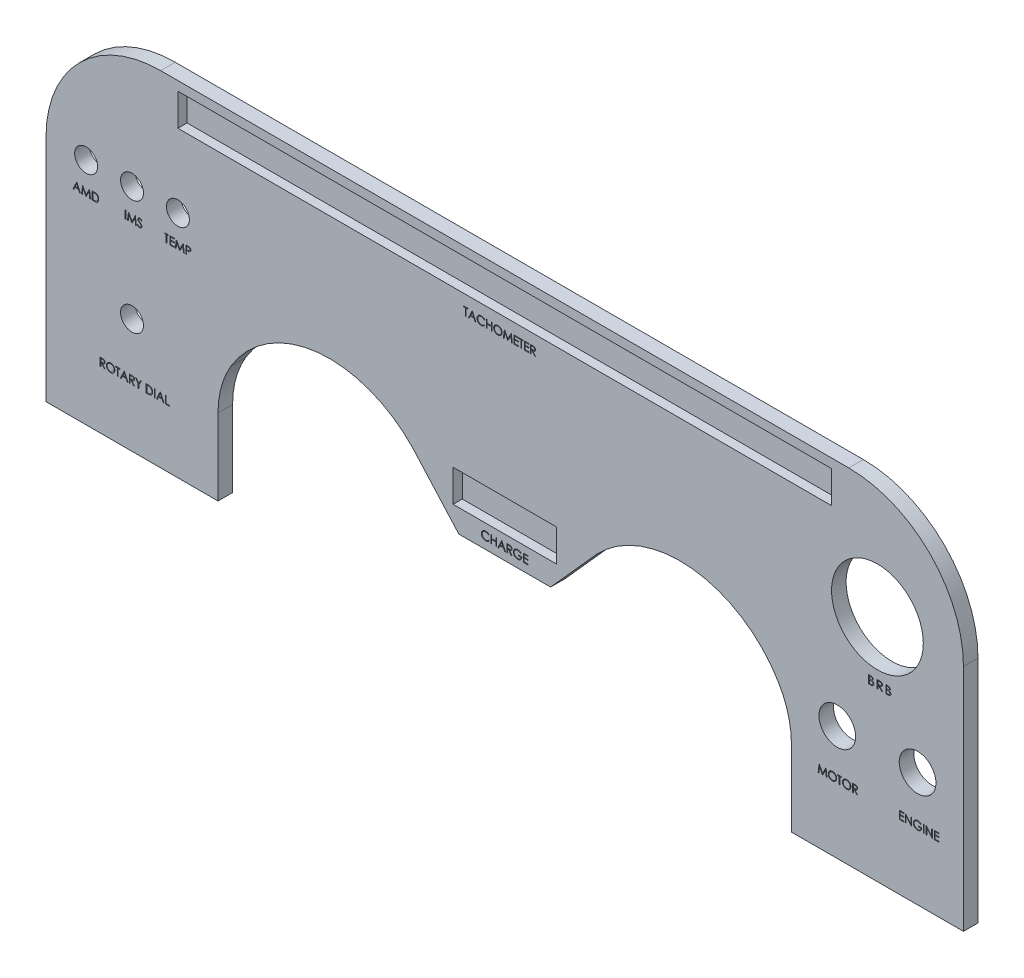
SolidWorks part; units mm, degrees
ref_plane "Front Plane" through (0, 0, 0) normal (0, 0, 1) x (1, 0, 0)
ref_plane "Top Plane" through (0, 0, 0) normal (0, 1, 0) x (1, 0, 0)
ref_plane "Right Plane" through (0, 0, 0) normal (1, 0, 0) x (0, 0, -1)
sketch "Sketch1" plane through (0, 0, 0) normal (0, 0, 1) x (1, 0, 0)
  line L0 (0, 0) -> (75, 0)
  line L1 (400, 0) -> (400, 150)
  line L2 (400, 150) -> (0, 150)
  line L3 (0, 150) -> (0, 0)
  line L4 (200, 150) -> (200, 40) construction
  line L5 (75, 0) -> (75, 40)
  line L6 (75, 40) -> (325, 40)
  line L7 (325, 0) -> (325, 40)
  line L8 (325, 0) -> (400, 0)
  line L9 (180, 40) -> (160, 62.3607)
  line L10 (220, 40) -> (240, 62.3607)
  arc A0 (75, 40) -> (160, 62.3607) centre (123.5673, 28.1166) cw
  arc A1 (325, 40) -> (240, 62.3607) centre (276.4327, 28.1166) ccw
  point P11 (200, 40)
  point P15 (110.8468, 76.4714)
  dimension "D7" = 30
  dimension "D8" = 50
  dimension "D1" = 400
  dimension "D2" = 150
  dimension "D3" = 40
  dimension "D4" = 125
  dimension "D5" = 20
  dimension "D6" = 40
extrude "Boss-Extrude1" add sketch "Sketch1" along normal blind 6.35 contours L4 L2 L3 L0 L5 A0 L9 L6 | L2 L4 L6 L10 A1 L7 L8 L1 region at (88.4336, 89.8407, 0) region at (311.5664, 89.8407, 0)
fillet "Fillet1" radius 50 2 edges at (400, 150, 3.175) (0, 150, 3.175)
sketch "Sketch2" plane through (0, 0, 6.35) normal (0, 0, 1) x (1, 0, 0)
  line L0 (0, 100) -> (0, 0) construction
  line L1 (0, 0) -> (75, 0) construction
  line L2 (325, 0) -> (400, 0) construction
  line L3 (400, 0) -> (400, 100) construction
  line L4 (350, 150) -> (50, 150) construction
  line L9 (180, 40) -> (220, 40) construction
  line L14 (200, 40) -> (200, 150) construction
  circle A2 centre (362.5, 100) radius 20
  circle A6 centre (37.5, 50) radius 5
  circle A7 centre (37.5, 100) radius 5
  circle A8 centre (17.5, 100) radius 5
  circle A9 centre (57.5, 100) radius 5
  circle A10 centre (345, 50) radius 8
  circle A11 centre (380, 50) radius 8
  dimension "D1" = 40
  dimension "D2" = 10
  dimension "D3" = 10
  dimension "D4" = 10
  dimension "D10" = 37.5
  dimension "D12" = 10
  dimension "D16" = 16
  dimension "D17" = 16
  dimension "D5" = 100
  dimension "D6" = 100
  dimension "D7" = 100
  dimension "D8" = 37.5
  dimension "D9" = 50
  dimension "D11" = 20
  dimension "D13" = 20
  dimension "D14" = 100
  dimension "D15" = 37.5
  dimension "D18" = 20
  dimension "D19" = 35
  dimension "D20" = 50
  dimension "D21" = 50
extrude "Cut-Extrude1" cut sketch "Sketch2" against normal through all contours A6
extrude "Cut-Extrude3" cut sketch "Sketch2<6>" against normal through all
sketch "Sketch2<6>" plane through (0, 0, 6.35) normal (0, 0, 1) x (1, 0, 0) same geometry as "Sketch2"
fillet "Fillet2" radius 40 1 edges at (75, 40, 3.175)
fillet "Fillet3" radius 40 1 edges at (325, 40, 3.175)
sketch "Sketch3" plane through (0, 0, 6.35) normal (0, 0, 1) x (1, 0, 0)
  text T0 "BRB" font "Century Gothic" height 3.5
extrude "Cut-Extrude4" cut sketch "Sketch3" against normal blind 2
sketch "Sketch4" plane through (0, 0, 6.35) normal (0, 0, 1) x (1, 0, 0)
  text T0 "MOTOR             ENGINE" font "Century Gothic" height 3.5
sketch "Sketch5" plane through (0, 0, 6.35) normal (0, 0, 1) x (1, 0, 0)
  text T0 "ROTARY DIAL"
sketch "Sketch6" plane through (0, 0, 6.35) normal (0, 0, 1) x (1, 0, 0)
  text T0 "AMD        IMS       TEMP"
extrude "Cut-Extrude5" cut sketch "Sketch6" against normal blind 2
extrude "Cut-Extrude6" cut sketch "Sketch5" against normal blind 2
extrude "Cut-Extrude7" cut sketch "Sketch4" against normal blind 2
sketch "Sketch7" plane through (0, 0, 6.35) normal (0, 0, 1) x (1, 0, 0)
  line L0 (350, 150) -> (50, 150) construction
  line L1 (57.5, 146) -> (342.5, 146)
  line L2 (57.5, 146) -> (57.5, 132)
  line L3 (57.5, 132) -> (342.5, 132)
  line L4 (342.5, 146) -> (342.5, 132)
  line L5 (200, 40) -> (200, 150) construction
  line L6 (180, 40) -> (220, 40) construction
  line L8 (177.5, 64) -> (222.5, 64)
  line L9 (177.5, 64) -> (177.5, 50)
  line L10 (177.5, 50) -> (222.5, 50)
  line L11 (222.5, 64) -> (222.5, 50)
  point P14 (222.5, 57)
  dimension "D1" = 14
  dimension "D2" = 4
  dimension "D3" = 285
  dimension "D4" = 142.5
  dimension "D5" = 14
  dimension "D6" = 45
  dimension "D7" = 22.5
  dimension "D8" = 10
extrude "Cut-Extrude8" cut sketch "Sketch7" against normal blind 4 contours L9 L8 L11 L10 | L2 L1 L4 L3
sketch "Sketch8" plane through (0, 0, 6.35) normal (0, 0, 1) x (1, 0, 0)
  text T0 "CHARGE"
extrude "Cut-Extrude9" cut sketch "Sketch8" against normal blind 2
sketch "Sketch9" plane through (0, 0, 6.35) normal (0, 0, 1) x (1, 0, 0)
  text T0 "TACHOMETER"
extrude "Cut-Extrude10" cut sketch "Sketch9" against normal blind 2
